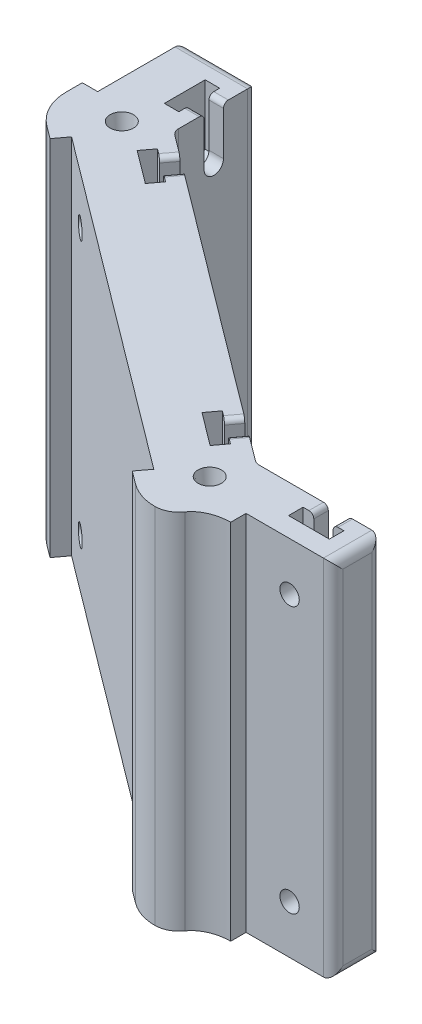
SolidWorks part; units mm, degrees
ref_plane "Front Plane" through (0, 0, 0) normal (0, 0, 1) x (1, 0, 0)
ref_plane "Top Plane" through (0, 0, 0) normal (0, 1, 0) x (1, 0, 0)
ref_plane "Right Plane" through (0, 0, 0) normal (1, 0, 0) x (0, 0, -1)
sketch "Sketch1" plane through (0, 0, 0) normal (0, 1, 0) x (1, 0, 0)
  line L0 (0, -10) -> (0, -6.825) construction
  line L2 (28.6667, -1.825) -> (28.6667, 86) construction
  line L3 (-6, -8) -> (-4.095, -5.46) construction
  line L6 (-4.095, -5.46) -> (0, 0) construction
  line L7 (0, -10) -> (-3.3333, -10) construction
  line L8 (0, 0) -> (0, -6.825) construction
  line L9 (-3.1623, -9.4868) -> (0, 0) construction
  line L10 (0, 0) -> (28.6667, 86) construction
  line L12 (-18.0283, 23.74) -> (2.725, 8.175)
  line L13 (28.6667, -1.825) -> (28.6667, 8.175)
  line L14 (28.6667, 8.175) -> (2.725, 8.175)
  line L15 (-6, -8) -> (-8.6667, -6)
  line L16 (-8.6667, -6) -> (-6.7617, -3.46)
  line L18 (10.6667, -5) -> (10.6667, -1.825)
  line L19 (-74.7617, 47.54) -> (-6.7617, -3.46)
  line L20 (-6.7617, -3.46) -> (-4.095, -5.46) construction
  line L22 (10.6667, -1.825) -> (28.6667, -1.825)
  line L23 (-6, -8) -> (-79.3333, 47) construction
  line L24 (-3.3333, -10) -> (-6, -8) construction
  line L25 (-8.6667, -6) -> (-83.3333, 50) construction
  line L26 (-74.7617, 47.54) -> (-76.6667, 45)
  line L27 (-76.6667, 45) -> (-79.3333, 47)
  line L28 (-83.3333, 50) -> (-83.3333, 76.3333) construction
  line L29 (-83.3333, 55) -> (-83.3333, 58.3333)
  line L30 (-83.3333, 58.3333) -> (-80.1583, 58.3333)
  line L31 (-80.1583, 58.3333) -> (-80.1583, 76.3333)
  line L32 (28.6667, 86) -> (-27.0283, 11.74) construction
  line L33 (-80.1583, 76.3333) -> (-65.1583, 76.3333)
  line L34 (-65.1583, 76.3333) -> (-65.1583, 59.0875)
  line L35 (-82.2776, 50.5279) -> (-65.1583, 59.0875) construction
  line L36 (-65.1583, 59.0875) -> (-51.3617, 48.74)
  line L37 (-51.3617, 48.74) -> (-60.3617, 36.74) construction
  line L38 (-51.3617, 48.74) -> (-18.0283, 23.74)
  line L39 (-83.3333, 76.3333) -> (-80.1583, 76.3333) construction
  arc A0 (0, -10) -> (-6, -8) centre (0, 0) cw
  arc A1 (-83.3333, 55) -> (-79.3333, 47) centre (-73.3333, 55) ccw
  arc A2 (0, -10) -> (4.1098, -7.8477) centre (0, -5) ccw
  ellipse E0 centre (10.6667, -10) end of major axis (3.4023, -10) minor radius 5 (4.1098, -7.8477) -> (10.6667, -5) cw
  dimension "D1" = 10
  dimension "D3" = 60
  dimension "D7" = 3.3333
  dimension "D8" = 5
  dimension "D9" = 3.175
  dimension "D2" = 15
  dimension "D4" = 18
  dimension "D5" = 10.6667
  dimension "D6" = 5
  dimension "D10" = 3.175
  dimension "D11" = 80
  dimension "D12" = 18
extrude "Boss-Extrude1" add sketch "Sketch1" along normal blind 75
sketch "Sketch2" plane through (0, 0, 1.825) normal (0, 0, 1) x (1, 0, 0)
  line L0 (19.6667, 0) -> (19.6667, 75) construction
  line L1 (10.6667, 0) -> (28.6667, 0) construction
  line L2 (10.6667, 75) -> (28.6667, 75) construction
  circle A0 centre (19.6667, 10) radius 2
  circle A1 centre (19.6667, 65) radius 2
  dimension "D1" = 4
  dimension "D2" = 10
  dimension "D3" = 10
extrude "Cut-Extrude1" cut sketch "Sketch2" against normal up to surface (10 mm away) up to face at (15.6958, 37.5, -8.175)
sketch "Sketch3" plane through (-4.095, 0, 5.46) normal (-0.6, 0, 0.8) x (0.8, 0, 0.6)
  line L0 (-12.3333, 0) -> (-12.3333, 75) construction
  line L1 (-88.3333, 0) -> (-3.3333, 0) construction
  line L2 (-88.3333, 75) -> (-3.3333, 75) construction
  line L3 (-3.3333, 75) -> (-3.3333, 0) construction
  line L4 (-45.8333, 0) -> (-45.8333, 75) construction
  line L5 (-88.3333, 0) -> (-3.3333, 0) construction
  line L6 (-88.3333, 75) -> (-3.3333, 75) construction
  circle A0 centre (-12.3333, 10) radius 2
  circle A1 centre (-12.3333, 65) radius 2
  circle A2 centre (-79.3333, 10) radius 2
  circle A3 centre (-79.3333, 65) radius 2
  dimension "D1" = 4
  dimension "D3" = 10
  dimension "D2" = 10
  dimension "D4" = 9
extrude "Cut-Extrude2" cut sketch "Sketch3" against normal up to surface (15 mm away) up to face at (-31.2167, 37.5, -33.6312)
sketch "Sketch4" plane through (-80.1583, 0, 0) normal (-1, 0, 0) x (0, 0, 1)
  line L0 (-67.3333, 0) -> (-67.3333, 75) construction
  line L1 (-76.3333, 0) -> (-58.3333, 0) construction
  line L2 (-76.3333, 75) -> (-58.3333, 75) construction
  circle A0 centre (-67.3333, 10) radius 2
  circle A1 centre (-67.3333, 65) radius 2
  dimension "D1" = 4
  dimension "D2" = 10
  dimension "D3" = 10
extrude "Cut-Extrude3" cut sketch "Sketch4" against normal up to surface (15 mm away) up to face at (-65.1583, 37.5, -67.7104)
sketch "Sketch6" plane through (4.905, 0, -6.54) normal (0.6, 0, -0.8) x (-0.8, 0, -0.6)
  line L0 (8.1146, 62.5643) -> (12.3333, 60.1286)
  line L1 (12.3333, 60.1286) -> (16.5521, 62.5643) construction
  line L2 (16.5521, 62.5643) -> (16.5521, 67.4357) construction
  line L3 (16.5521, 67.4357) -> (12.3333, 69.8714) construction
  line L4 (12.3333, 69.8714) -> (8.1146, 67.4357) construction
  line L5 (8.1146, 67.4357) -> (8.1146, 62.5643) construction
  line L6 (8.1146, 62.5643) -> (12.3333, 60.1286) construction
  line L7 (12.3333, 5.1286) -> (16.5521, 7.5643) construction
  line L8 (16.5521, 7.5643) -> (16.5521, 12.4357) construction
  line L9 (16.5521, 12.4357) -> (12.3333, 14.8714) construction
  line L10 (12.3333, 14.8714) -> (8.1146, 12.4357) construction
  line L11 (8.1146, 12.4357) -> (8.1146, 7.5643) construction
  line L12 (8.1146, 7.5643) -> (12.3333, 5.1286) construction
  line L13 (79.3333, 5.1286) -> (83.5521, 7.5643) construction
  line L14 (83.5521, 7.5643) -> (83.5521, 12.4357) construction
  line L15 (83.5521, 12.4357) -> (79.3333, 14.8714) construction
  line L16 (79.3333, 14.8714) -> (75.1146, 12.4357) construction
  line L17 (75.1146, 12.4357) -> (75.1146, 7.5643) construction
  line L18 (75.1146, 7.5643) -> (79.3333, 5.1286) construction
  line L19 (79.3333, 60.1286) -> (83.5521, 62.5643) construction
  line L20 (83.5521, 62.5643) -> (83.5521, 67.4357) construction
  line L21 (83.5521, 67.4357) -> (79.3333, 69.8714) construction
  line L22 (79.3333, 69.8714) -> (75.1146, 67.4357) construction
  line L23 (75.1146, 67.4357) -> (75.1146, 62.5643) construction
  line L24 (75.1146, 62.5643) -> (79.3333, 60.1286) construction
  line L25 (12.3333, 60.1286) -> (16.5521, 62.5643)
  line L26 (16.5521, 62.5643) -> (16.5521, 75)
  line L27 (2.725, 75) -> (87.5792, 75) construction
  line L28 (16.5521, 75) -> (8.1146, 75)
  line L29 (8.1146, 75) -> (8.1146, 62.5643)
  line L30 (75.1146, 62.5643) -> (79.3333, 60.1286)
  line L31 (79.3333, 60.1286) -> (83.5521, 62.5643)
  line L32 (83.5521, 62.5643) -> (83.5521, 75)
  line L33 (83.5521, 75) -> (75.1146, 75)
  line L34 (75.1146, 75) -> (75.1146, 62.5643)
  line L35 (8.1146, 12.4357) -> (12.3333, 14.8714)
  line L36 (12.3333, 14.8714) -> (16.5521, 12.4357)
  line L37 (16.5521, 12.4357) -> (16.5521, 0)
  line L38 (2.725, 0) -> (87.5792, 0) construction
  line L39 (16.5521, 0) -> (8.1146, 0)
  line L40 (8.1146, 0) -> (8.1146, 12.4357)
  line L41 (75.1146, 12.4357) -> (79.3333, 14.8714)
  line L42 (79.3333, 14.8714) -> (83.5521, 12.4357)
  line L43 (83.5521, 12.4357) -> (83.5521, 0)
  line L44 (83.5521, 0) -> (75.1146, 0)
  line L45 (75.1146, 0) -> (75.1146, 12.4357)
  circle A0 centre (12.3333, 65) radius 4.2187 construction
  circle A1 centre (12.3333, 10) radius 4.2188 construction
  circle A2 centre (79.3333, 10) radius 4.2187 construction
  circle A3 centre (79.3333, 65) radius 4.2187 construction
  dimension "D1" = 8.4375
extrude "Cut-Extrude5" cut sketch "Sketch6" against normal blind 3 from offset 3 offset against normal yes
sketch "Sketch7" plane through (4.905, 0, -6.54) normal (0.6, 0, -0.8) x (-0.8, 0, -0.6)
  line L0 (14.3333, 65) -> (14.3333, 75)
  line L1 (2.725, 75) -> (87.5792, 75) construction
  line L2 (14.3333, 75) -> (10.3333, 75)
  line L3 (10.3333, 75) -> (10.3333, 65)
  line L4 (81.3333, 65) -> (81.3333, 75)
  line L5 (81.3333, 0) -> (77.3333, 0)
  line L6 (2.725, 37.5) -> (87.5792, 37.5) construction
  line L7 (2.725, 75) -> (2.725, 0) construction
  line L8 (87.5792, 75) -> (87.5792, 0) construction
  line L18 (81.3333, 75) -> (77.3333, 75)
  line L19 (77.3333, 75) -> (77.3333, 65)
  line L20 (81.3333, 10) -> (81.3333, 0)
  line L21 (77.3333, 0) -> (77.3333, 10)
  line L22 (14.3333, 0) -> (10.3333, 0)
  line L23 (14.3333, 10) -> (14.3333, 0)
  line L24 (10.3333, 0) -> (10.3333, 10)
  arc A0 (10.3333, 65) -> (14.3333, 65) centre (12.3333, 65) cw
  circle A1 centre (12.3333, 65) radius 2 construction
  arc A5 (77.3333, 65) -> (81.3333, 65) centre (79.3333, 65) cw
  circle A6 centre (79.3333, 65) radius 2 construction
  arc A7 (77.3333, 10) -> (81.3333, 10) centre (79.3333, 10) ccw
  arc A8 (10.3333, 10) -> (14.3333, 10) centre (12.3333, 10) ccw
extrude "Cut-Extrude6" cut sketch "Sketch7" against normal blind 3
sketch "Sketch8" plane through (0, 0, -8.175) normal (0, 0, -1) x (-1, 0, 0)
  line L0 (-23.8854, 0) -> (-23.8854, 12.4357)
  line L1 (-19.6667, 60.1286) -> (-15.4479, 62.5643) construction
  line L2 (-15.4479, 62.5643) -> (-15.4479, 67.4357) construction
  line L3 (-15.4479, 67.4357) -> (-19.6667, 69.8714) construction
  line L4 (-19.6667, 69.8714) -> (-23.8854, 67.4357) construction
  line L5 (-23.8854, 67.4357) -> (-23.8854, 62.5643) construction
  line L6 (-23.8854, 62.5643) -> (-19.6667, 60.1286) construction
  line L7 (-19.6667, 5.1286) -> (-15.4479, 7.5643) construction
  line L8 (-15.4479, 7.5643) -> (-15.4479, 12.4357) construction
  line L9 (-15.4479, 12.4357) -> (-19.6667, 14.8714) construction
  line L10 (-19.6667, 14.8714) -> (-23.8854, 12.4357) construction
  line L11 (-23.8854, 12.4357) -> (-23.8854, 7.5643) construction
  line L12 (-23.8854, 7.5643) -> (-19.6667, 5.1286) construction
  line L13 (-28.6667, 0) -> (-2.725, 0) construction
  line L14 (-23.8854, 12.4357) -> (-19.6667, 14.8714)
  line L15 (-19.6667, 14.8714) -> (-15.4479, 12.4357)
  line L16 (-15.4479, 12.4357) -> (-15.4479, 0)
  line L17 (-15.4479, 0) -> (-23.8854, 0)
  line L18 (-23.8854, 62.5643) -> (-19.6667, 60.1286)
  line L19 (-19.6667, 60.1286) -> (-15.4479, 62.5643)
  line L20 (-15.4479, 62.5643) -> (-15.4479, 75)
  line L21 (-28.6667, 75) -> (-2.725, 75) construction
  line L22 (-15.4479, 75) -> (-23.8854, 75)
  line L23 (-23.8854, 75) -> (-23.8854, 62.5643)
  circle A0 centre (-19.6667, 65) radius 4.2187 construction
  circle A1 centre (-19.6667, 10) radius 4.2188 construction
  dimension "D1" = 8.4375
extrude "Cut-Extrude7" cut sketch "Sketch8" against normal blind 3 from offset 3 offset against normal yes
sketch "Sketch9" plane through (0, 0, -8.175) normal (0, 0, -1) x (-1, 0, 0)
  line L0 (-17.6667, 65) -> (-17.6667, 75)
  line L1 (-28.6667, 75) -> (-2.725, 75) construction
  line L2 (-17.6667, 75) -> (-21.6667, 75)
  line L3 (-21.6667, 75) -> (-21.6667, 65)
  line L4 (-21.6667, 10) -> (-21.6667, 0)
  line L5 (-28.6667, 0) -> (-2.725, 0) construction
  line L6 (-21.6667, 0) -> (-17.6667, 0)
  line L7 (-17.6667, 0) -> (-17.6667, 10)
  arc A0 (-21.6667, 65) -> (-17.6667, 65) centre (-19.6667, 65) cw
  circle A1 centre (-19.6667, 65) radius 2 construction
  arc A2 (-21.6667, 10) -> (-17.6667, 10) centre (-19.6667, 10) ccw
  circle A3 centre (-19.6667, 10) radius 2 construction
extrude "Cut-Extrude8" cut sketch "Sketch9" against normal blind 3
sketch "Sketch10" plane through (-65.1583, 0, 0) normal (1, 0, 0) x (0, 0, -1)
  line L0 (63.1146, 62.5643) -> (67.3333, 60.1286)
  line L1 (67.3333, 60.1286) -> (71.5521, 62.5643) construction
  line L2 (71.5521, 62.5643) -> (71.5521, 67.4357) construction
  line L3 (71.5521, 67.4357) -> (67.3333, 69.8714) construction
  line L4 (67.3333, 69.8714) -> (63.1146, 67.4357) construction
  line L5 (63.1146, 67.4357) -> (63.1146, 62.5643) construction
  line L6 (63.1146, 62.5643) -> (67.3333, 60.1286) construction
  line L7 (67.3333, 5.1286) -> (71.5521, 7.5643) construction
  line L8 (71.5521, 7.5643) -> (71.5521, 12.4357) construction
  line L9 (71.5521, 12.4357) -> (67.3333, 14.8714) construction
  line L10 (67.3333, 14.8714) -> (63.1146, 12.4357) construction
  line L11 (63.1146, 12.4357) -> (63.1146, 7.5643) construction
  line L12 (63.1146, 7.5643) -> (67.3333, 5.1286) construction
  line L13 (67.3333, 60.1286) -> (71.5521, 62.5643)
  line L14 (71.5521, 62.5643) -> (71.5521, 75)
  line L15 (59.0875, 75) -> (76.3333, 75) construction
  line L16 (71.5521, 75) -> (63.1146, 75)
  line L17 (63.1146, 75) -> (63.1146, 62.5643)
  line L18 (63.1146, 12.4357) -> (67.3333, 14.8714)
  line L19 (67.3333, 14.8714) -> (71.5521, 12.4357)
  line L20 (71.5521, 12.4357) -> (71.5521, 0)
  line L21 (59.0875, 0) -> (76.3333, 0) construction
  line L22 (71.5521, 0) -> (63.1146, 0)
  line L23 (63.1146, 0) -> (63.1146, 12.4357)
  circle A0 centre (67.3333, 65) radius 4.2188 construction
  circle A1 centre (67.3333, 10) radius 4.2188 construction
  dimension "D1" = 8.4375
extrude "Cut-Extrude9" cut sketch "Sketch10" against normal blind 3 from offset 3 offset against normal yes
sketch "Sketch5" plane through (0, 75, 0) normal (0, 1, 0) x (1, 0, 0)
  line L0 (-3.1623, -9.4868) -> (2.725, 8.175) construction
  line L1 (-82.2776, 50.5279) -> (-65.1583, 59.0875) construction
  line L2 (-72.3333, 55.5) -> (0.3333, 1) construction
  line L3 (-74.7617, 47.54) -> (-6.7617, -3.46) construction
  line L4 (-8.6667, -6) -> (-6, -8) construction
  arc A0 (-6, -8) -> (0, -10) centre (0, 0) ccw construction
  arc A1 (-83.3333, 55) -> (-79.3333, 47) centre (-73.3333, 55) ccw construction
  circle A2 centre (0.3333, 1) radius 2.413
  circle A3 centre (-72.3333, 55.5) radius 2.413
  dimension "D1" = 4.826
  dimension "D2" = 11
extrude "Cut-Extrude4" cut sketch "Sketch5" against normal blind 6.35 draft 8 contours A2 | A3
sketch "Sketch11" plane through (-65.1583, 0, 0) normal (1, 0, 0) x (0, 0, -1)
  line L0 (69.3333, 65) -> (69.3333, 75)
  line L1 (59.0875, 75) -> (76.3333, 75) construction
  line L2 (69.3333, 75) -> (65.3333, 75)
  line L3 (65.3333, 75) -> (65.3333, 65)
  line L4 (69.3333, 10) -> (69.3333, 0)
  line L5 (59.0875, 0) -> (76.3333, 0) construction
  line L6 (69.3333, 0) -> (65.3333, 0)
  line L7 (65.3333, 0) -> (65.3333, 10)
  arc A0 (65.3333, 65) -> (69.3333, 65) centre (67.3333, 65) cw
  circle A1 centre (67.3333, 65) radius 2 construction
  arc A2 (65.3333, 10) -> (69.3333, 10) centre (67.3333, 10) ccw
  circle A3 centre (67.3333, 10) radius 2 construction
extrude "Cut-Extrude10" cut sketch "Sketch11" against normal blind 3
sketch "Sketch14" plane through (0, 68.65, 0) normal (0, 1, 0) x (1, 0, 0)
  circle A0 centre (-72.3333, 55.5) radius 1.5206
  circle A1 centre (0.3333, 1) radius 1.5206
  circle A2 centre (-72.3333, 55.5) radius 1.5206 construction
extrude "Cut-Extrude12" cut sketch "Sketch14" against normal blind 5
ref_plane "Plane1" through (0, 37.5, 0) normal (0, 1, 0) x (1, 0, 0)
mirror "Mirror1" about plane through (0, 37.5, 0) normal (0, 1, 0) of "Cut-Extrude4", "Cut-Extrude12"
fillet "Fillet1" radius 1 16 edges at (-66.6583, 75, -69.3333) (-66.6583, 75, -65.3333) (-57.8617, 75, -51.74) (-61.0617, 75, -54.14) (-66.6583, 0, -69.3333) (-66.6583, 0, -65.3333) (-61.0617, 0, -54.14) (-57.8617, 0, -51.74) (-7.4617, 0, -13.94) (-4.2617, 0, -11.54) (21.6667, 0, -6.675) (17.6667, 0, -6.675) (-7.4617, 75, -13.94) (-4.2617, 75, -11.54) (17.6667, 75, -6.675) (21.6667, 75, -6.675)
fillet "Fillet2" radius 2 10 edges at (28.6667, 75, -3.175) (-72.6583, 75, -76.3333) (-72.6583, 0, -76.3333) (28.6667, 0, -3.175) (-80.1583, 37.5, -76.3333) (-65.1583, 37.5, -76.3333) (-65.1583, 37.5, -59.0875) (2.725, 37.5, -8.175) (28.6667, 37.5, -8.175) (28.6667, 37.5, 1.825)
equation "\"0.25i\"=3"
